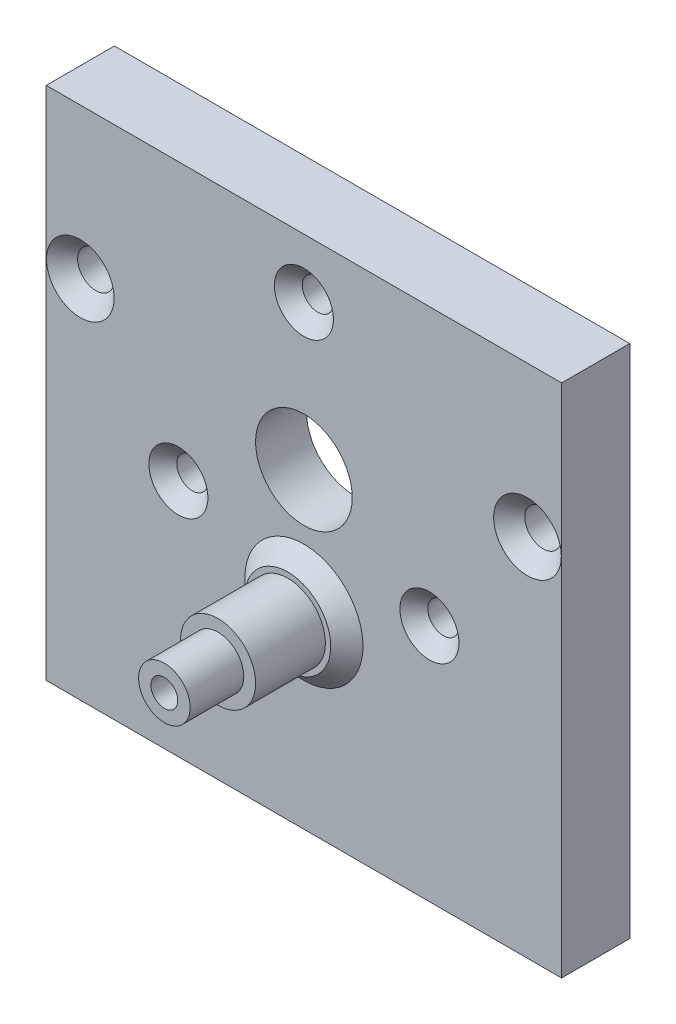
SolidWorks part; units mm, degrees
material "Liga 1060"
ref_plane "Plano frontal" through (0, 0, 0) normal (0, 0, 1) x (1, 0, 0)
ref_plane "Plano superior" through (0, 0, 0) normal (0, 1, 0) x (1, 0, 0)
ref_plane "Plano direito" through (0, 0, 0) normal (1, 0, 0) x (0, 0, -1)
sketch "Esboço1" plane through (0, 0, 0) normal (0, 0, 1) x (1, 0, 0)
  line L0 (24, 0) -> (24, 48) construction
  line L1 (0, 0) -> (48, 0)
  line L2 (0, 0) -> (0, 48)
  line L3 (0, 48) -> (48, 48)
  line L4 (48, 0) -> (48, 48)
  dimension "D1" = 48
  dimension "D2" = 48
extrude "Ressalto-extrusão1" add sketch "Esboço1" along normal blind 6.35
sketch "Esboço3" plane through (0, 0, 6.35) normal (0, 0, 1) x (1, 0, 0)
  line L0 (24, 48) -> (24, 0) construction
  line L1 (48, 48) -> (0, 48) construction
  line L2 (0, 0) -> (48, 0) construction
  circle A0 centre (24, 17.5) radius 6
  point P6 (24, 17.5)
  dimension "D2" = 12
  dimension "D1" = 17.5
extrude "Ressalto-extrusão2" add sketch "Esboço3" along normal blind 13
sketch "Esboço4" plane through (0, 0, 19.35) normal (0, 0, 1) x (1, 0, 0)
  circle A0 centre (24, 17.5) radius 6
  circle A1 centre (24, 17.5) radius 2.4
  dimension "D1" = 12
  dimension "D2" = 4.8
extrude "Corte-extrusão1" cut sketch "Esboço4" against normal blind 5
sketch "Esboço5" plane through (0, 0, 14.35) normal (0, 0, 1) x (1, 0, 0)
  circle A0 centre (24, 17.5) radius 6
  circle A1 centre (24, 17.5) radius 3.5
  dimension "D1" = 7
  dimension "D2" = 12
extrude "Corte-extrusão2" cut sketch "Esboço5" against normal blind 6.5
sketch "Esboço10" plane through (0, 0, 19.35) normal (0, 0, 1) x (1, 0, 0)
  point P0 (24, 17.5)
hole_wizard "Furo roscado de M31" positions "3DSketch3" profile "Esboço11" tap size "M3" standard "ISO"
sketch3d "3DSketch3"
  point P0 (24, 17.5, 19.35)
sketch "Esboço11" plane through (24, 17.5, 19.35) normal (1, 0, 0) x (0, -1, 0)
  line L0 (0, 0) -> (0, 9.2511)
  line L1 (0, 9.2511) -> (1.25, 8.5)
  line L2 (1.25, 8.5) -> (1.25, 0)
  line L5 (1.25, 0) -> (0, 0)
  line L10 (0, 9.2511) -> (-1.25, 8.5) construction
  line L11 (0, -6.35) -> (0, 107.95) construction
  dimension "Tap Drill Dia." = 2.5
  dimension "Tap Drill Depth" = 8.5
  dimension "Drill Angle" = 118
cosmetic thread "Rosca de furo1" parameters "D1"=6, "D2"=3
sketch "Esboço12" plane through (0, 0, 0) normal (0, 0, -1) x (-1, 0, 0)
  line L0 (-24, 17.5) -> (-24, 29) construction
  circle A0 centre (-24, 29) radius 17.5
  dimension "D2" = 35
  dimension "D1" = 11.5
sketch "Esboço15" plane through (0, 0, 6.35) normal (0, 0, 1) x (1, 0, 0)
  line L0 (0, 48) -> (3.175, 48) construction
  line L1 (48, 48) -> (0, 48) construction
  line L2 (3.175, 48) -> (3.175, 28) construction
  line L3 (48, 48) -> (44.825, 48) construction
  line L4 (44.825, 48) -> (44.825, 28) construction
  point P5 (3.175, 34)
  point P10 (44.825, 34)
  dimension "D1" = 3.175
  dimension "D2" = 20
  dimension "D3" = 14
  dimension "D4" = 3.175
  dimension "D5" = 20
  dimension "D6" = 14
sketch "Esboço17" plane through (0, 0, 0) normal (0, -1, 0) x (1, 0, 0)
  line L0 (3.175, 6.35) -> (3.175, 0) construction
  line L1 (0, 0) -> (48, 0) construction
  line L2 (44.825, 6.35) -> (44.825, 0) construction
  point P8 (3.175, 3.175)
  point P9 (44.825, 3.175)
hole_wizard "Escareado para parafuso com cabeça escareada chata de M31" positions "3DSketch6" profile "Esboço19" countersink size "M3" standard "ISO"
sketch3d "3DSketch6"
  line L0 (44.825, 0, 6.35) -> (44.825, 0, 0) construction
  point P0 (44.825, 34, 6.35)
  point P3 (3.175, 34, 6.35)
  point P6 (44.825, 0, 3.175)
  point P10 (44.825, 0, 3.175)
sketch "Esboço19" plane through (44.825, 34, 6.35) normal (1, 0, 0) x (0, -1, 0)
  line L0 (0, 0) -> (0, 11.8)
  line L1 (0, 11.8) -> (1.7, 10.7785)
  line L2 (1.7, 10.7785) -> (1.7, 1.45)
  line L3 (1.7, 1.45) -> (3.15, 0)
  line L5 (3.15, 0) -> (0, 0)
  line L6 (-1.7, 1.45) -> (-3.15, 0) construction
  line L10 (0, 11.8) -> (-1.7, 10.7785) construction
  line L11 (0, -6.35) -> (0, 107.95) construction
  dimension "Hole Dia." = 3.4
  dimension "Hole Depth" = 11.8
  dimension "Near C'Sink Dia." = 6.3
  dimension "Near C'Sink Angle" = 90
  dimension "Drill Angle" = 118
hole_wizard "Furo roscado de M32" positions "3DSketch8" profile "Esboço21" tap size "M3" standard "ISO"
sketch3d "3DSketch8"
  point P0 (3.175, 0, 3.175)
  point P3 (44.825, 0, 3.175)
sketch "Esboço21" plane through (3.175, 0, 3.175) normal (1, 0, 0) x (0, 0, -1)
  line L0 (0, 0) -> (0, 10)
  line L1 (0, 10) -> (1.25, 9.2489)
  line L2 (1.25, 9.2489) -> (1.25, 0)
  line L5 (1.25, 0) -> (0, 0)
  line L10 (0, 10) -> (-1.25, 9.2489) construction
  line L11 (0, -6.35) -> (0, 107.95) construction
  dimension "Tap Drill Dia." = 2.5
  dimension "Tap Drill Depth" = 10
  dimension "Drill Angle" = 118
cosmetic thread "Rosca de furo2" parameters "D1"=6, "D2"=3
cosmetic thread "Rosca de furo3" parameters "D1"=6, "D2"=3
chamfer "Chanfro4" distance 2 angle 45 1 edges at (30, 17.5, 7.85)
sketch "Esboço29" plane through (0, 0, 6.35) normal (0, 0, 1) x (1, 0, 0)
  circle A0 centre (24, 29) radius 4.5
  dimension "D1" = 9
extrude "Corte-extrusão3" cut sketch "Esboço29" against normal through all
sketch "Esboço30" plane through (0, 0, 6.35) normal (0, 0, 1) x (1, 0, 0)
  line L0 (24, 29) -> (24, 42.5) construction
  line L1 (24, 29) -> (35.6913, 22.25) construction
  line L2 (24, 29) -> (12.3087, 22.25) construction
  circle A0 centre (24, 29) radius 13.5
  dimension "D1" = 27
  dimension "D3" = 120
  dimension "D2" = 120
hole_wizard "Escareado para parafuso com cabeça escareada chata de M2.51" positions "3DSketch9" profile "Esboço31" countersink size "M2.5" standard "ISO" end condition through all
sketch3d "3DSketch9"
  point P0 (12.3087, 22.25, 6.35)
  point P3 (35.6913, 22.25, 6.35)
  point P6 (24, 42.5, 6.35)
sketch "Esboço31" plane through (12.3087, 22.25, 6.35) normal (1, 0, 0) x (0, -1, 0)
  line L0 (0, 0) -> (0, 6.35)
  line L1 (0, 6.35) -> (1.45, 6.35)
  line L2 (1.45, 6.35) -> (1.45, 1.3)
  line L3 (1.45, 1.3) -> (2.75, 0)
  line L5 (2.75, 0) -> (0, 0)
  line L6 (-1.45, 1.3) -> (-2.75, 0) construction
  line L11 (0, -6.35) -> (0, 107.95) construction
  dimension "Thru Hole Dia." = 2.9
  dimension "Thru Hole Depth" = 6.35
  dimension "Near C'Sink Dia." = 5.5
  dimension "Near C'Sink Angle" = 90
sketch "Esboço32" plane through (0, 0, 0) normal (0, 0, -1) x (-1, 0, 0)
  circle A0 centre (-24, 29) radius 17.5
  dimension "D1" = 35
extrude "Corte-extrusão4" cut sketch "Esboço32" against normal blind 1.6
